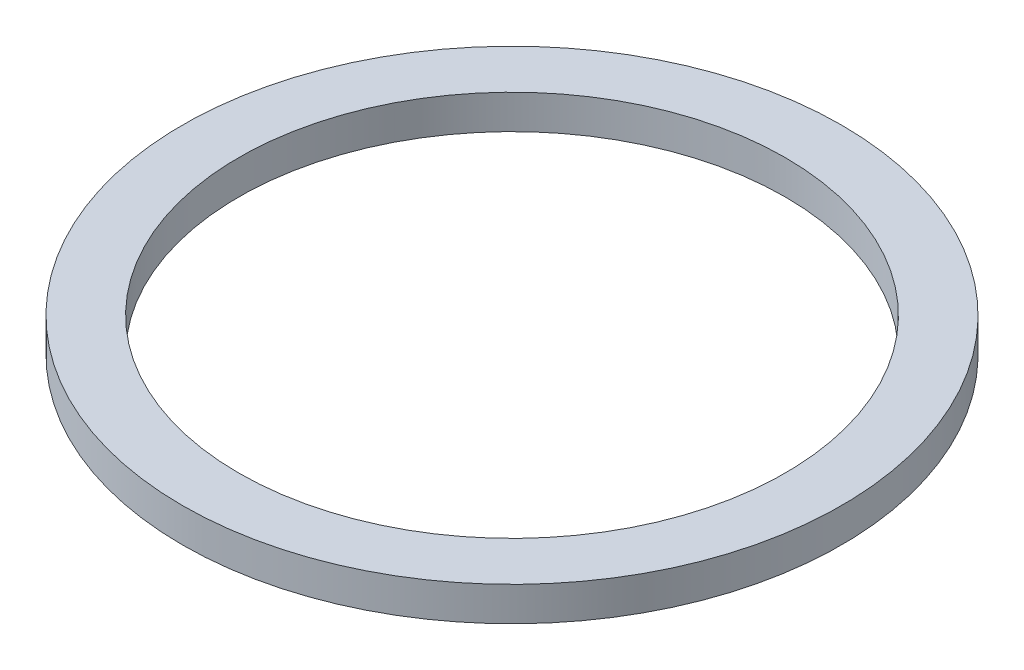
SolidWorks part; units mm, degrees
ref_plane "Front Plane" through (0, 0, 0) normal (0, 0, 1) x (1, 0, 0)
ref_plane "Top Plane" through (0, 0, 0) normal (0, 1, 0) x (1, 0, 0)
ref_plane "Right Plane" through (0, 0, 0) normal (1, 0, 0) x (0, 0, -1)
sketch "Sketch1" plane through (0, 0, 0) normal (0, 1, 0) x (1, 0, 0)
  circle A0 centre (0, 0) radius 22.21
  circle A2 centre (0, 0) radius 18.415
  dimension "D1" = 44.42
  dimension "D2" = 36.83
extrude "Boss-Extrude1" add sketch "Sketch1" along normal blind 2.3
equation "\"can_outer_diameter\"= 44.42mm"
equation "\"D1@Sketch1\"=\"can_outer_diameter\""
equation "\"can_thickness\"= 2.3"
equation "\"can_height\"=104.902"
equation "\"neck_diameter\"=36.83"
equation "\"D2@Sketch1\"=\"neck_diameter\""
equation "\"D1@Boss-Extrude1\"=\"can_thickness\""
